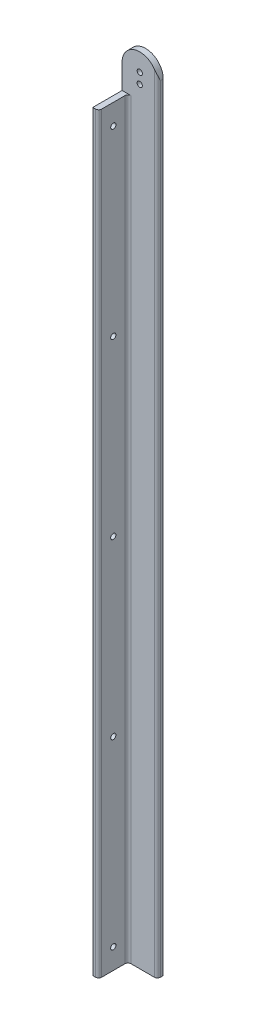
SolidWorks part; units mm, degrees
material "6061 Alloy"
ref_plane "Front Plane" through (0, 0, 0) normal (0, 0, 1) x (1, 0, 0)
ref_plane "Top Plane" through (0, 0, 0) normal (0, 1, 0) x (1, 0, 0)
ref_plane "Right Plane" through (0, 0, 0) normal (1, 0, 0) x (0, 0, -1)
sketch "Sketch2" plane through (0, 0, 0) normal (0, 1, 0) x (1, 0, 0)
  line L0 (0, 0) -> (19.05, 0)
  line L1 (0, 0) -> (0, 19.05)
  line L2 (4.7625, 3.175) -> (17.4625, 3.175)
  line L3 (3.175, 4.7625) -> (3.175, 17.4625)
  line L4 (0, 19.05) -> (1.5875, 19.05)
  line L5 (19.05, 1.5875) -> (19.05, 0)
  line L6 (3.175, 3.175) -> (3.175, 19.05) construction
  line L7 (3.175, 3.175) -> (19.05, 3.175) construction
  arc A0 (3.175, 17.4625) -> (1.5875, 19.05) centre (1.5875, 17.4625) ccw
  arc A1 (3.175, 4.7625) -> (4.7625, 3.175) centre (4.7625, 4.7625) ccw
  arc A2 (17.4625, 3.175) -> (19.05, 1.5875) centre (17.4625, 1.5875) cw
  dimension "D2" = 1.5875
  dimension "D1" = 3.175
extrude "Boss-Extrude1" add sketch "Sketch2" along normal blind 431.8
sketch "Sketch4" plane through (3.175, 0, 0) normal (1, 0, 0) x (0, 0, -1)
  line L0 (19.05, 431.8) -> (19.05, 406.4)
  line L1 (19.05, 431.8) -> (19.05, 0) construction
  line L2 (19.05, 406.4) -> (3.175, 406.4)
  line L3 (3.175, 431.8) -> (3.175, 0) construction
  line L4 (3.175, 406.4) -> (3.175, 431.8)
  line L5 (3.175, 431.8) -> (19.05, 431.8)
extrude "Cut-Extrude1" cut sketch "Sketch4" against normal blind 6.35
sketch "Sketch5" plane through (3.175, 0, 0) normal (-1, 0, 0) x (0, 0, 1)
  line L8 (-4.7625, 406.4) -> (-3.175, 406.4)
  line L9 (-3.175, 406.4) -> (-3.175, 431.8)
  line L10 (-3.175, 431.8) -> (-4.7625, 431.8)
  line L11 (-4.7625, 431.8) -> (-4.7625, 406.4)
  line L12 (-4.7625, 406.4) -> (-3.175, 406.4)
  line L13 (-3.175, 406.4) -> (-3.175, 431.8)
  line L14 (-3.175, 431.8) -> (-4.7625, 431.8)
  line L15 (-4.7625, 431.8) -> (-4.7625, 406.4)
  dimension "D1" = 0
extrude "Cut-Extrude2" cut sketch "Sketch5" against normal blind 6.35
sketch "Sketch6" plane through (3.175, 0, 0) normal (1, 0, 0) x (0, 0, -1)
  line L0 (19.05, 0) -> (3.175, 0) construction
  line L1 (11.1125, 0) -> (11.1125, 15.875) construction
  line L2 (19.05, 406.4) -> (3.175, 406.4) construction
  line L3 (11.1125, 406.4) -> (11.1125, 390.525) construction
  line L4 (11.1125, 15.875) -> (11.1125, 203.2) construction
  line L5 (11.1125, 203.2) -> (11.1125, 390.525) construction
  circle A1 centre (11.1125, 109.5375) radius 1.4224
  circle A2 centre (11.1125, 203.2) radius 1.4224
  circle A3 centre (11.1125, 296.8625) radius 1.4224
  circle A5 centre (11.1125, 11.1125) radius 1.4224
  circle A6 centre (11.1125, 395.2875) radius 1.4224
  point P12 (11.1125, 203.2)
  point P13 (11.1125, 296.8625)
  point P15 (11.1125, 109.5375)
  dimension "D2" = 2.8448
  dimension "D3" = 2.8448
  dimension "D4" = 2.8448
  dimension "D6" = 2.8448
  dimension "D7" = 2.8448
extrude "Cut-Extrude3" cut sketch "Sketch6" against normal blind 5.08
sketch "Sketch7" plane through (0, 431.8, 0) normal (0, 1, 0) x (1, 0, 0)
  line L8 (17.4625, 3.175) -> (0, 3.175)
  line L9 (0, 3.175) -> (0, 0)
  line L10 (0, 0) -> (19.05, 0)
  line L11 (19.05, 0) -> (19.05, 1.5875)
  line L12 (17.4625, 3.175) -> (0, 3.175)
  line L13 (0, 3.175) -> (0, 0)
  line L14 (0, 0) -> (19.05, 0)
  line L15 (19.05, 0) -> (19.05, 1.5875)
  arc A2 (19.05, 1.5875) -> (17.4625, 3.175) centre (17.4625, 1.5875) ccw
  arc A3 (19.05, 1.5875) -> (17.4625, 3.175) centre (17.4625, 1.5875) ccw
  dimension "D1" = 0
extrude "Cut-Extrude4" cut sketch "Sketch7" against normal blind 2.54
sketch "Sketch8" plane through (0, 0, -3.175) normal (0, 0, -1) x (-1, 0, 0)
  line L0 (0, 429.26) -> (0, 419.735) construction
  line L1 (0, 429.26) -> (0, 406.4) construction
  line L2 (0, 419.735) -> (-9.525, 419.735) construction
  line L3 (-9.525, 419.735) -> (-9.525, 414.02) construction
  circle A0 centre (-9.525, 419.735) radius 1.4224
  circle A1 centre (-9.525, 414.02) radius 1.4224
  dimension "D1" = 2.8448
  dimension "D3" = 2.8448
  dimension "D2" = 5.715
extrude "Cut-Extrude5" cut sketch "Sketch8" against normal blind 5.08
ref_plane "Plane1" through (0, 0, 2.54) normal (0, 0, 1) x (1, 0, 0)
mirror "Mirror3" about plane through (0, 0, 2.54) normal (0, 0, 1) of bodies 106
sketch "Sketch9" plane through (0, 0, 2.54) normal (0, 0, 1) x (1, 0, 0)
  line L1 (-6.6248, 469.5409) -> (22.2362, 469.5409)
  line L2 (-6.6248, 469.5409) -> (-6.6248, -77.9837)
  line L3 (-6.6248, -77.9837) -> (22.2362, -77.9837)
  line L4 (22.2362, 469.5409) -> (22.2362, -77.9837)
extrude "Cut-Extrude6" cut sketch "Sketch9" against normal blind 30.48
sketch "Sketch10" plane through (0, 0, 8.255) normal (0, 0, 1) x (1, 0, 0)
  line L0 (9.525, 419.735) -> (9.525, 415.925) construction
  line L7 (19.05, 419.735) -> (19.05, 429.26)
  line L8 (19.05, 429.26) -> (0, 429.26)
  line L9 (0, 419.735) -> (0, 429.26)
  line L11 (19.05, 429.26) -> (9.525, 419.735) construction
  line L12 (9.525, 419.735) -> (0, 429.26) construction
  arc A3 (19.05, 419.735) -> (0, 419.735) centre (9.525, 419.735) ccw
  line M4 (17.4625, 429.26) -> (0, 429.26)
  line M5 (0, 429.26) -> (0, 406.4)
  line M9 (17.4625, 0) -> (17.4625, 429.26)
extrude "Cut-Extrude7" cut sketch "Sketch10" against normal blind 5.08 contours M9 | M9 M4 | M5 region at (18.3487, 426.1569, 8.255) region at (2.1276, 427.1324, 8.255) region at (15.5776, 428.0522, 8.255)
